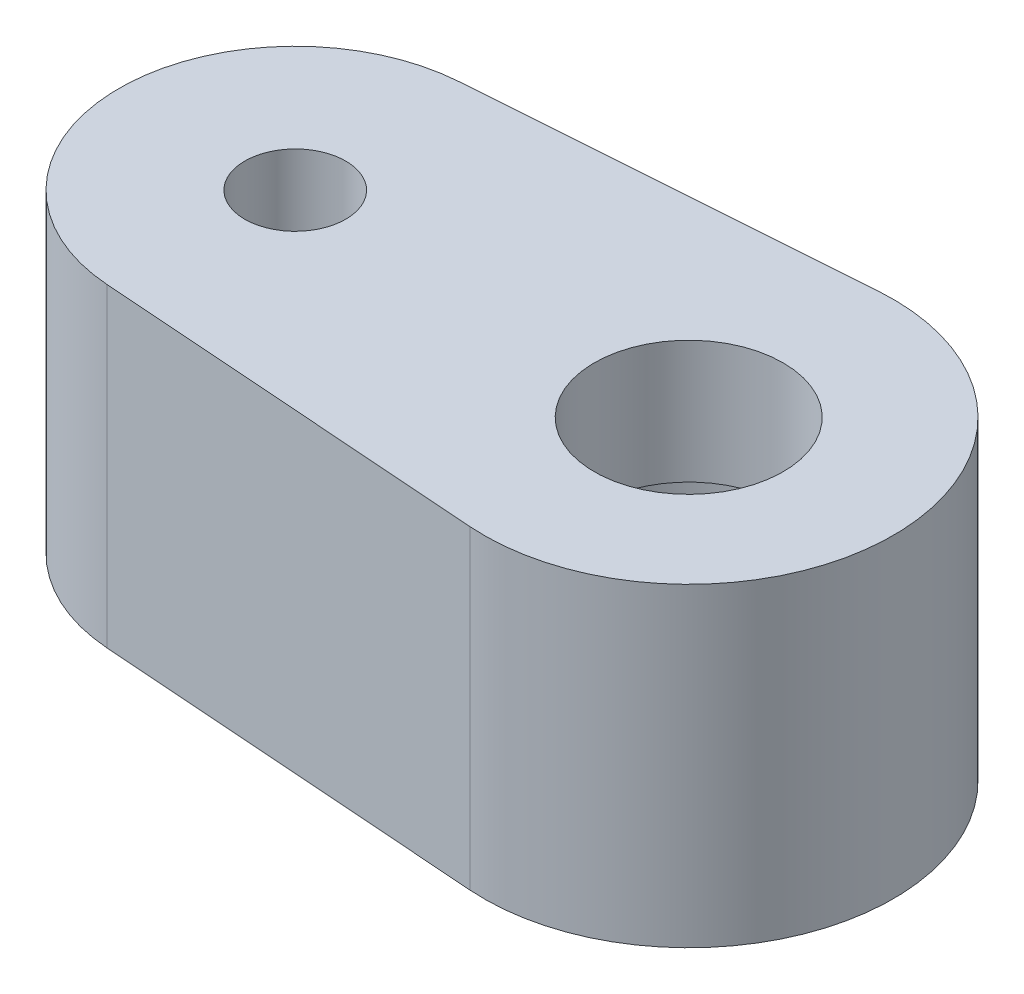
SolidWorks part; units mm, degrees
ref_plane "Front Plane" through (0, 0, 0) normal (0, 0, 1) x (1, 0, 0)
ref_plane "Top Plane" through (0, 0, 0) normal (0, 1, 0) x (1, 0, 0)
ref_plane "Right Plane" through (0, 0, 0) normal (1, 0, 0) x (0, 0, -1)
sketch "Sketch1" plane through (0, 0, 0) normal (0, 1, 0) x (1, 0, 0)
  line L0 (-2.5806, 1.1171) -> (-0.0936, 1.2966)
  line L1 (-2.5806, -1.1171) -> (-0.0936, -1.2966)
  line L2 (-2.5, 0) -> (0, 0) construction
  arc A0 (-0.0936, -1.2966) -> (-0.0936, 1.2966) centre (0, 0) ccw
  arc A1 (-2.5806, 1.1171) -> (-2.5806, -1.1171) centre (-2.5, 0) ccw
  dimension "D1" = 2.24
  dimension "D2" = 2.6
  dimension "D3" = 2.5
extrude "Boss-Extrude1" add sketch "Sketch1" along normal blind 1 and the other way blind 1
sketch "Sketch4" plane through (0, 0, 0) normal (0, 0, 1) x (1, 0, 0)
  line L0 (0.85, 0) -> (0.85, 0.075)
  line L1 (0.85, 0.075) -> (0.6, 0.2193)
  line L2 (0.6, 0.2193) -> (0.6, 1)
  line L3 (1.3, 1) -> (-0.0936, 1) construction
  line L4 (0, 0) -> (0.85, 0) construction
  line L5 (0.85, 0) -> (0.85, -0.075)
  line L6 (0.85, -0.075) -> (0.6, -0.2193)
  line L7 (-0.0936, -1) -> (1.3, -1) construction
  line L9 (0, -1) -> (0, 1)
  line L10 (0, 1) -> (0.6, 1)
  line L11 (0.6, -0.2193) -> (0.6, -1)
  line L12 (0, -1) -> (0.6, -1)
  dimension "D1" = 0.075
  dimension "D2" = 120
  dimension "D3" = 0.25
  dimension "D4" = 0.6
revolve "Cut-Revolve1" cut sketch "Sketch4" angle 360 about L9
sketch "Sketch5" plane through (0, 1, 0) normal (0, 1, 0) x (1, 0, 0)
  circle A0 centre (-2.5, 0) radius 0.3207
  dimension "D1" = 0.6414
extrude "Cut-Extrude1" cut sketch "Sketch5" against normal up to next
